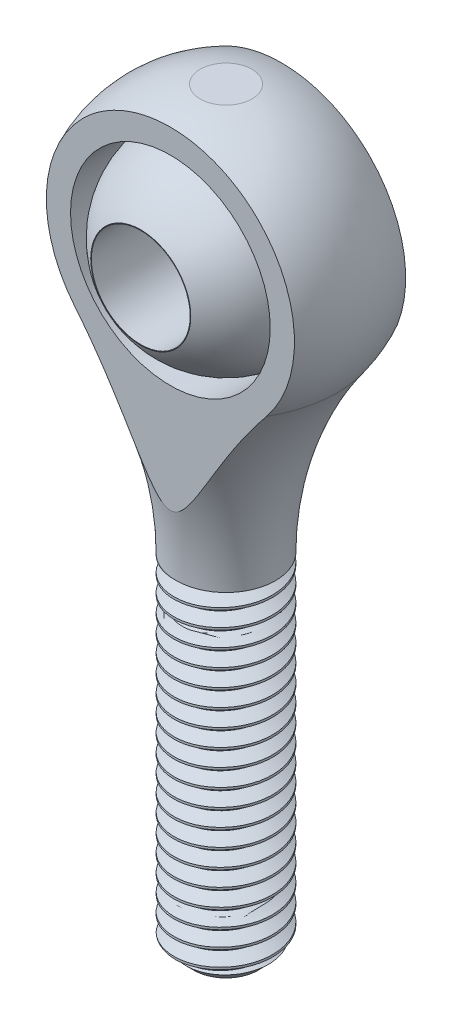
SolidWorks part; units mm, degrees
ref_plane "Front" through (0, 0, 0) normal (0, 0, 1) x (1, 0, 0)
ref_plane "Top" through (0, 0, 0) normal (0, 1, 0) x (1, 0, 0)
ref_plane "Right" through (0, 0, 0) normal (1, 0, 0) x (0, 0, -1)
sketch "Sketch1" plane through (0, 0, 0) normal (0, 0, 1) x (1, 0, 0)
  line L0 (0, 0) -> (0, -14)
  line L1 (0, -14) -> (2, -14)
  line L2 (2, -14) -> (2, 0)
  line L3 (2, 0) -> (0, 0)
  line L5 (0, 16.5) -> (0, 0) construction
  line L6 (0, 16.5) -> (5.5, 16.5) construction
  line L7 (5.5, 16.5) -> (5.5, 11) construction
  line L8 (-2, -14) -> (-2, 0) construction
  line L9 (5.5, 16.4) -> (0, 16.4) construction
  arc A0 (4.4887, 7.8218) -> (0, 16.5) centre (0, 11) ccw construction
  circle A1 centre (0, 11) radius 2 construction
  circle A2 centre (0, 11) radius 4 construction
  circle A3 centre (0, 11) radius 4.04 construction
  arc A4 (2, 0) -> (4.4887, 7.8218) centre (15.5357, 0) cw construction
  point P16 (-2, -9.975)
  dimension "A" = 4
  dimension "Ball Dia" = 8
  dimension "B" = 11
  dimension "D1" = 8.08
  dimension "D" = 25
  dimension "E" = 14
  dimension "Thread Dia" = 4
  dimension "D2" = 4.025
  dimension "D3" = 30.4
revolve "Revolve1" add sketch "Sketch1" angle 360 about L5
sketch "Sketch12" plane through (0, -14, 0) normal (0, -1, 0) x (1, 0, 0)
  circle A1 centre (0, 0) radius 2
  circle A2 centre (0, 0) radius 2
  dimension "D1" = 0
curve "Helix/Spiral1" pitch 0.7 height 14.7 turns 21 parameters "pitch"=0.7
chamfer "Chamfer2" distance 0.7 angle 45 1 edges at (-2, -14, 0)
sketch "Sketch13" plane through (0, 0, 0) normal (1, 0, 0) x (0, 0, -1)
  line L0 (-2, -14.6125) -> (-2, -14)
  line L1 (-2, -14) -> (-1.5453, -14.2625)
  line L2 (-1.5453, -14.2625) -> (-1.5453, -14.35)
  line L3 (-1.5453, -14.35) -> (-2, -14.6125)
  line L4 (-1.5453, -14.3063) -> (-2, -14.3063) construction
  line L5 (-1.7727, -14.4813) -> (-1.7727, -14.1313) construction
  line L6 (-2, -14) -> (2, -14) construction
  dimension "D1" = 60
  dimension "D3" = 0.35
sweep "Cut-Sweep1" cut profiles "Sketch13" path "Helix/Spiral1"
sketch "Sketch4" plane through (0, 0, 0) normal (0, 0, 1) x (1, 0, 0)
  line L0 (2, 0) -> (0, 0) construction
  line L2 (0, 16.5) -> (0, 0) construction
  line L3 (2, 0) -> (0, 0)
  line L5 (0, 16.5) -> (0, 0)
  line L6 (0, 16.5) -> (0, 19.04) construction
  arc A0 (4.4887, 7.8218) -> (0, 16.5) centre (0, 11) ccw construction
  arc A1 (4.4887, 7.8218) -> (0, 16.5) centre (0, 11) ccw
  arc A2 (4.4887, 7.8218) -> (2, 0) centre (15.5357, 0) ccw construction
  arc A3 (4.4887, 7.8218) -> (2, 0) centre (15.5357, 0) ccw
  dimension "D1" = 2.54
revolve "Revolve2" add sketch "Sketch4" angle 360 about L6
sketch "Sketch5" plane through (0, 0, 0) normal (1, 0, 0) x (0, 0, -1)
  line L0 (2.25, 16.5) -> (5.5, 16.5)
  line L1 (-2.25, 16.5) -> (2.25, 16.5) construction
  line L2 (-2.25, 16.5) -> (-2.25, 0.9)
  line L3 (-2, 0) -> (2, 0) construction
  line L4 (2.25, 16.5) -> (2.25, 0.9)
  line L5 (5.5, 16.5) -> (5.5, 0)
  line L6 (5.5, 0) -> (2, 0)
  line L7 (-2, 0) -> (-5.5, 0)
  line L8 (-5.5, 0) -> (-5.5, 16.5)
  line L9 (-5.5, 16.5) -> (-2.25, 16.5)
  line L10 (2, 0) -> (2.25, 0.9)
  line L11 (-2, 0) -> (-2.25, 0.9)
  line L12 (-2.25, 0.9) -> (2.25, 0.9) construction
  line L13 (0, 0) -> (0, 0.9) construction
  arc A0 (4.4887, 7.8218) -> (-4.4887, 7.8218) centre (0, 11) ccw construction
  dimension "F" = 4.5
  dimension "D2" = 0.9
  dimension "D1" = 4
extrude "Cut-Extrude1" cut sketch "Sketch5" against normal through all and the other way through all
sketch "Sketch6" plane through (0, 0, 0) normal (0, 0, 1) x (1, 0, 0)
  circle A0 centre (0, 11) radius 4.04 construction
  circle A1 centre (0, 11) radius 4.04
extrude "Cut-Extrude2" cut sketch "Sketch6" against normal through all and the other way through all
sketch "Sketch7" plane through (0, 0, 0) normal (0, 0, 1) x (1, 0, 0)
  line L0 (0, 15) -> (0, 7)
  line L1 (0, 16.5) -> (0, 0) construction
  line L2 (0, 0) -> (0, 7) construction
  arc A0 (0, 7) -> (0, 15) centre (0, 11) ccw
  circle A1 centre (0, 11) radius 4 construction
revolve "Revolve3" add sketch "Sketch7" angle 360 about L2
sketch "Sketch8" plane through (0, 0, 0) normal (1, 0, 0) x (0, 0, -1)
  line L0 (-2.25, 16.5) -> (2.25, 16.5) construction
  line L1 (-3.45, 16.5) -> (3.45, 16.5) construction
  line L2 (-3.45, 16.5) -> (-3.45, 0)
  line L3 (-3.45, 0) -> (3.45, 0) construction
  line L4 (3.45, 16.5) -> (3.45, 0)
  line L5 (3.45, 16.5) -> (5.5, 16.5)
  line L6 (5.5, 16.5) -> (5.5, 0)
  line L7 (5.5, 0) -> (3.45, 0)
  line L8 (-3.45, 0) -> (-5.5, 0)
  line L9 (-5.5, 0) -> (-5.5, 16.5)
  line L10 (-5.5, 16.5) -> (-3.45, 16.5)
  dimension "C" = 6.9
extrude "Cut-Extrude3" cut sketch "Sketch8" against normal through all and the other way through all
sketch "Sketch10" plane through (0, 0, 0) normal (0, 0, 1) x (1, 0, 0)
  circle A0 centre (0, 11) radius 2 construction
  circle A1 centre (0, 11) radius 2
extrude "Cut-Extrude4" cut sketch "Sketch10" against normal through all and the other way through all
chamfer "Chamfer1" [suppressed] distance 0.2 angle 45
sketch "Sketch11" plane through (0, 0, 0) normal (1, 0, 0) x (0, 0, -1)
  line L0 (0, 11) -> (-3.45, 11.9244) construction
  line L1 (2.25, 11) -> (-2.25, 11) construction
  line L2 (0, 11) -> (-3.45, 10.0756) construction
  line L3 (0, 16.5) -> (0, 0) construction
  line L4 (-3.45, 16.5) -> (-3.45, 0) construction
  line L5 (0, 11) -> (0.0074, 11) construction
  dimension "Swivel" = 30
sketch "Sketch14" plane through (0, 0, 0) normal (0, 0, 1) x (1, 0, 0)
  line L1 (5.5, 16.5) -> (-5.5, 16.5)
  line L2 (5.5, 16.5) -> (5.5, 16.4)
  line L3 (5.5, 16.4) -> (-5.5, 16.4)
  line L4 (-5.5, 16.5) -> (-5.5, 16.4)
extrude "Cut-Extrude5" cut sketch "Sketch14" against normal through all both and the other way through all
equation "\"D1@Sketch1\"=\"Ball Dia@Sketch1\"*1.01"
equation "\"D1@Chamfer1\"=\"A@Sketch1\"/20"
equation "\"D1@Sketch5\"=\"Thread Dia@Sketch1\""
equation "\"D2@Sketch5\"=\"F@Sketch5\"/5"
equation "\"D2@Sketch13\" = \"pitch@Helix/Spiral1\"*.125"
equation "\"D3@Sketch13\" = \"pitch@Helix/Spiral1\"*.50"
equation "\"D3@Helix/Spiral1\" = \"E@Sketch1\"+\"pitch@Helix/Spiral1\""
equation "\"D1@Chamfer2\" = \"pitch@Helix/Spiral1\""
equation "\"D2@Sketch1\" = \"pitch@Helix/Spiral1\"*5.75"
